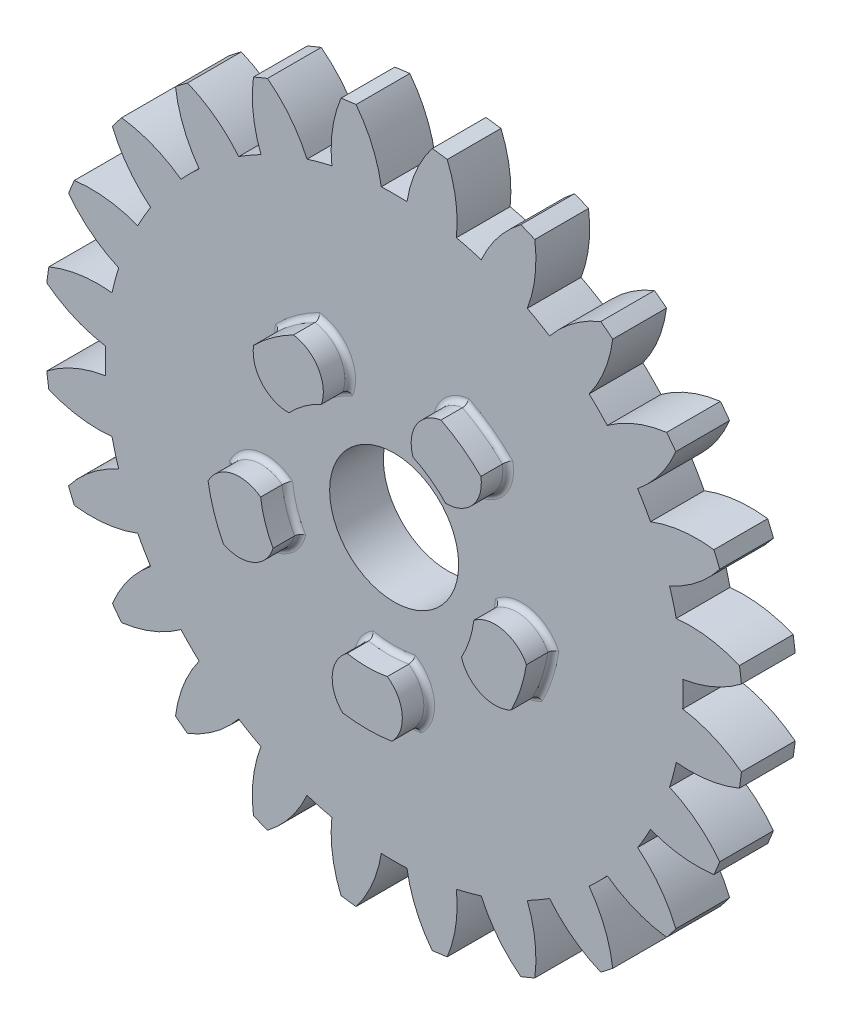
SolidWorks part; units mm, degrees
ref_plane "Front Plane" through (0, 0, 0) normal (0, 0, 1) x (1, 0, 0)
ref_plane "Top Plane" through (0, 0, 0) normal (0, 1, 0) x (1, 0, 0)
ref_plane "Right Plane" through (0, 0, 0) normal (1, 0, 0) x (0, 0, -1)
sketch "Sketch1" plane through (0, 0, 0) normal (0, 0, 1) x (1, 0, 0)
  circle A0 centre (0, 0) radius 3
  arc A96 (-32.3065, 3.5416) -> (-26.8474, 1.1963) centre (-24.9877, 13.0513) ccw
  arc A97 (-26.8474, 1.1963) -> (-26.8474, -1.1963) centre (0, 0) ccw
  arc A98 (-26.8474, -1.1963) -> (-32.3065, -3.5416) centre (-24.9877, -13.0513) ccw
  arc A99 (-32.3065, -3.5416) -> (-32.1223, -4.9406) centre (0, 0) ccw
  arc A100 (-32.1223, -4.9406) -> (-26.2422, -5.7931) centre (-27.5142, 6.1393) ccw
  arc A101 (-26.2422, -5.7931) -> (-25.6229, -8.1041) centre (0, 0) ccw
  arc A102 (-25.6229, -8.1041) -> (-30.289, -11.7824) centre (-20.7583, -19.0739) ccw
  arc A103 (-30.289, -11.7824) -> (-29.749, -13.0861) centre (0, 0) ccw
  arc A104 (-29.749, -13.0861) -> (-23.8486, -12.3877) centre (-28.1656, -1.191) ccw
  arc A105 (-23.8486, -12.3877) -> (-22.6523, -14.4597) centre (0, 0) ccw
  arc A106 (-22.6523, -14.4597) -> (-26.2074, -19.2203) centre (-15.1143, -23.7966) ccw
  arc A107 (-26.2074, -19.2203) -> (-25.3484, -20.3398) centre (0, 0) ccw
  arc A108 (-25.3484, -20.3398) -> (-19.8299, -18.138) centre (-26.8976, -8.4403) ccw
  arc A109 (-19.8299, -18.138) -> (-18.138, -19.8299) centre (0, 0) ccw
  arc A110 (-18.138, -19.8299) -> (-20.3398, -25.3484) centre (-8.4403, -26.8976) ccw
  arc A111 (-20.3398, -25.3484) -> (-19.2203, -26.2074) centre (0, 0) ccw
  arc A112 (-19.2203, -26.2074) -> (-14.4597, -22.6523) centre (-23.7966, -15.1143) ccw
  arc A113 (-14.4597, -22.6523) -> (-12.3877, -23.8486) centre (0, 0) ccw
  arc A114 (-12.3877, -23.8486) -> (-13.0861, -29.749) centre (-1.191, -28.1656) ccw
  arc A115 (-13.0861, -29.749) -> (-11.7824, -30.289) centre (0, 0) ccw
  arc A116 (-11.7824, -30.289) -> (-8.1041, -25.6229) centre (-19.0739, -20.7583) ccw
  arc A117 (-8.1041, -25.6229) -> (-5.7931, -26.2422) centre (0, 0) ccw
  arc A118 (-5.7931, -26.2422) -> (-4.9406, -32.1223) centre (6.1393, -27.5142) ccw
  arc A119 (-4.9406, -32.1223) -> (-3.5416, -32.3065) centre (0, 0) ccw
  arc A120 (-3.5416, -32.3065) -> (-1.1963, -26.8474) centre (-13.0513, -24.9877) ccw
  arc A121 (-1.1963, -26.8474) -> (1.1963, -26.8474) centre (0, 0) ccw
  arc A122 (1.1963, -26.8474) -> (3.5416, -32.3065) centre (13.0513, -24.9877) ccw
  arc A123 (3.5416, -32.3065) -> (4.9406, -32.1223) centre (0, 0) ccw
  arc A124 (4.9406, -32.1223) -> (5.7931, -26.2422) centre (-6.1393, -27.5142) ccw
  arc A125 (5.7931, -26.2422) -> (8.1041, -25.6229) centre (0, 0) ccw
  arc A126 (8.1041, -25.6229) -> (11.7824, -30.289) centre (19.0739, -20.7583) ccw
  arc A127 (11.7824, -30.289) -> (13.0861, -29.749) centre (0, 0) ccw
  arc A128 (13.0861, -29.749) -> (12.3877, -23.8486) centre (1.191, -28.1656) ccw
  arc A129 (12.3877, -23.8486) -> (14.4597, -22.6523) centre (0, 0) ccw
  arc A130 (14.4597, -22.6523) -> (19.2203, -26.2074) centre (23.7966, -15.1143) ccw
  arc A131 (19.2203, -26.2074) -> (20.3398, -25.3484) centre (0, 0) ccw
  arc A132 (20.3398, -25.3484) -> (18.138, -19.8299) centre (8.4403, -26.8976) ccw
  arc A133 (18.138, -19.8299) -> (19.8299, -18.138) centre (0, 0) ccw
  arc A134 (19.8299, -18.138) -> (25.3484, -20.3398) centre (26.8976, -8.4403) ccw
  arc A135 (25.3484, -20.3398) -> (26.2074, -19.2203) centre (0, 0) ccw
  arc A136 (26.2074, -19.2203) -> (22.6523, -14.4597) centre (15.1143, -23.7966) ccw
  arc A137 (22.6523, -14.4597) -> (23.8486, -12.3877) centre (0, 0) ccw
  arc A138 (23.8486, -12.3877) -> (29.749, -13.0861) centre (28.1656, -1.191) ccw
  arc A139 (29.749, -13.0861) -> (30.289, -11.7824) centre (0, 0) ccw
  arc A140 (30.289, -11.7824) -> (25.6229, -8.1041) centre (20.7583, -19.0739) ccw
  arc A141 (25.6229, -8.1041) -> (26.2422, -5.7931) centre (0, 0) ccw
  arc A142 (26.2422, -5.7931) -> (32.1223, -4.9406) centre (27.5142, 6.1393) ccw
  arc A143 (32.1223, -4.9406) -> (32.3065, -3.5416) centre (0, 0) ccw
  arc A144 (32.3065, -3.5416) -> (26.8474, -1.1963) centre (24.9877, -13.0513) ccw
  arc A145 (26.8474, -1.1963) -> (26.8474, 1.1963) centre (0, 0) ccw
  arc A146 (26.8474, 1.1963) -> (32.3065, 3.5416) centre (24.9877, 13.0513) ccw
  arc A147 (32.3065, 3.5416) -> (32.1223, 4.9406) centre (0, 0) ccw
  arc A148 (32.1223, 4.9406) -> (26.2422, 5.7931) centre (27.5142, -6.1393) ccw
  arc A149 (26.2422, 5.7931) -> (25.6229, 8.1041) centre (0, 0) ccw
  arc A150 (25.6229, 8.1041) -> (30.289, 11.7824) centre (20.7583, 19.0739) ccw
  arc A151 (30.289, 11.7824) -> (29.749, 13.0861) centre (0, 0) ccw
  arc A152 (29.749, 13.0861) -> (23.8486, 12.3877) centre (28.1656, 1.191) ccw
  arc A153 (23.8486, 12.3877) -> (22.6523, 14.4597) centre (0, 0) ccw
  arc A154 (22.6523, 14.4597) -> (26.2074, 19.2203) centre (15.1143, 23.7966) ccw
  arc A155 (26.2074, 19.2203) -> (25.3484, 20.3398) centre (0, 0) ccw
  arc A156 (25.3484, 20.3398) -> (19.8299, 18.138) centre (26.8976, 8.4403) ccw
  arc A157 (19.8299, 18.138) -> (18.138, 19.8299) centre (0, 0) ccw
  arc A158 (18.138, 19.8299) -> (20.3398, 25.3484) centre (8.4403, 26.8976) ccw
  arc A159 (20.3398, 25.3484) -> (19.2203, 26.2074) centre (0, 0) ccw
  arc A160 (19.2203, 26.2074) -> (14.4597, 22.6523) centre (23.7966, 15.1143) ccw
  arc A161 (14.4597, 22.6523) -> (12.3877, 23.8486) centre (0, 0) ccw
  arc A162 (12.3877, 23.8486) -> (13.0861, 29.749) centre (1.191, 28.1656) ccw
  arc A163 (13.0861, 29.749) -> (11.7824, 30.289) centre (0, 0) ccw
  arc A164 (11.7824, 30.289) -> (8.1041, 25.6229) centre (19.0739, 20.7583) ccw
  arc A165 (8.1041, 25.6229) -> (5.7931, 26.2422) centre (0, 0) ccw
  arc A166 (5.7931, 26.2422) -> (4.9406, 32.1223) centre (-6.1393, 27.5142) ccw
  arc A167 (4.9406, 32.1223) -> (3.5416, 32.3065) centre (0, 0) ccw
  arc A168 (3.5416, 32.3065) -> (1.1963, 26.8474) centre (13.0513, 24.9877) ccw
  arc A169 (1.1963, 26.8474) -> (-1.1963, 26.8474) centre (0, 0) ccw
  arc A170 (-1.1963, 26.8474) -> (-3.5416, 32.3065) centre (-13.0513, 24.9877) ccw
  arc A171 (-3.5416, 32.3065) -> (-4.9406, 32.1223) centre (0, 0) ccw
  arc A172 (-4.9406, 32.1223) -> (-5.7931, 26.2422) centre (6.1393, 27.5142) ccw
  arc A173 (-5.7931, 26.2422) -> (-8.1041, 25.6229) centre (0, 0) ccw
  arc A174 (-8.1041, 25.6229) -> (-11.7824, 30.289) centre (-19.0739, 20.7583) ccw
  arc A175 (-11.7824, 30.289) -> (-13.0861, 29.749) centre (0, 0) ccw
  arc A176 (-13.0861, 29.749) -> (-12.3877, 23.8486) centre (-1.191, 28.1656) ccw
  arc A177 (-12.3877, 23.8486) -> (-14.4597, 22.6523) centre (0, 0) ccw
  arc A178 (-14.4597, 22.6523) -> (-19.2203, 26.2074) centre (-23.7966, 15.1143) ccw
  arc A179 (-19.2203, 26.2074) -> (-20.3398, 25.3484) centre (0, 0) ccw
  arc A180 (-20.3398, 25.3484) -> (-18.138, 19.8299) centre (-8.4403, 26.8976) ccw
  arc A181 (-18.138, 19.8299) -> (-19.8299, 18.138) centre (0, 0) ccw
  arc A182 (-19.8299, 18.138) -> (-25.3484, 20.3398) centre (-26.8976, 8.4403) ccw
  arc A183 (-25.3484, 20.3398) -> (-26.2074, 19.2203) centre (0, 0) ccw
  arc A184 (-26.2074, 19.2203) -> (-22.6523, 14.4597) centre (-15.1143, 23.7966) ccw
  arc A185 (-22.6523, 14.4597) -> (-23.8486, 12.3877) centre (0, 0) ccw
  arc A186 (-23.8486, 12.3877) -> (-29.749, 13.0861) centre (-28.1656, 1.191) ccw
  arc A187 (-29.749, 13.0861) -> (-30.289, 11.7824) centre (0, 0) ccw
  arc A188 (-30.289, 11.7824) -> (-25.6229, 8.1041) centre (-20.7583, 19.0739) ccw
  arc A189 (-25.6229, 8.1041) -> (-26.2422, 5.7931) centre (0, 0) ccw
  arc A190 (-26.2422, 5.7931) -> (-32.1223, 4.9406) centre (-27.5142, -6.1393) ccw
  arc A191 (-32.1223, 4.9406) -> (-32.3065, 3.5416) centre (0, 0) ccw
  arc A192 (-32.3065, 3.5416) -> (-26.8474, 1.1963) centre (-24.9877, 13.0513) ccw
  arc A193 (-26.8474, 1.1963) -> (-26.8474, -1.1963) centre (0, 0) ccw
  arc A194 (-26.8474, -1.1963) -> (-32.3065, -3.5416) centre (-24.9877, -13.0513) ccw
  arc A195 (-32.3065, -3.5416) -> (-32.1223, -4.9406) centre (0, 0) ccw
  arc A196 (-32.1223, -4.9406) -> (-26.2422, -5.7931) centre (-27.5142, 6.1393) ccw
  arc A197 (-26.2422, -5.7931) -> (-25.6229, -8.1041) centre (0, 0) ccw
  arc A198 (-25.6229, -8.1041) -> (-30.289, -11.7824) centre (-20.7583, -19.0739) ccw
  arc A199 (-30.289, -11.7824) -> (-29.749, -13.0861) centre (0, 0) ccw
  arc A200 (-29.749, -13.0861) -> (-23.8486, -12.3877) centre (-28.1656, -1.191) ccw
  arc A201 (-23.8486, -12.3877) -> (-22.6523, -14.4597) centre (0, 0) ccw
  arc A202 (-22.6523, -14.4597) -> (-26.2074, -19.2203) centre (-15.1143, -23.7966) ccw
  arc A203 (-26.2074, -19.2203) -> (-25.3484, -20.3398) centre (0, 0) ccw
  arc A204 (-25.3484, -20.3398) -> (-19.8299, -18.138) centre (-26.8976, -8.4403) ccw
  arc A205 (-19.8299, -18.138) -> (-18.138, -19.8299) centre (0, 0) ccw
  arc A206 (-18.138, -19.8299) -> (-20.3398, -25.3484) centre (-8.4403, -26.8976) ccw
  arc A207 (-20.3398, -25.3484) -> (-19.2203, -26.2074) centre (0, 0) ccw
  arc A208 (-19.2203, -26.2074) -> (-14.4597, -22.6523) centre (-23.7966, -15.1143) ccw
  arc A209 (-14.4597, -22.6523) -> (-12.3877, -23.8486) centre (0, 0) ccw
  arc A210 (-12.3877, -23.8486) -> (-13.0861, -29.749) centre (-1.191, -28.1656) ccw
  arc A211 (-13.0861, -29.749) -> (-11.7824, -30.289) centre (0, 0) ccw
  arc A212 (-11.7824, -30.289) -> (-8.1041, -25.6229) centre (-19.0739, -20.7583) ccw
  arc A213 (-8.1041, -25.6229) -> (-5.7931, -26.2422) centre (0, 0) ccw
  arc A214 (-5.7931, -26.2422) -> (-4.9406, -32.1223) centre (6.1393, -27.5142) ccw
  arc A215 (-4.9406, -32.1223) -> (-3.5416, -32.3065) centre (0, 0) ccw
  arc A216 (-3.5416, -32.3065) -> (-1.1963, -26.8474) centre (-13.0513, -24.9877) ccw
  arc A217 (-1.1963, -26.8474) -> (1.1963, -26.8474) centre (0, 0) ccw
  arc A218 (1.1963, -26.8474) -> (3.5416, -32.3065) centre (13.0513, -24.9877) ccw
  arc A219 (3.5416, -32.3065) -> (4.9406, -32.1223) centre (0, 0) ccw
  arc A220 (4.9406, -32.1223) -> (5.7931, -26.2422) centre (-6.1393, -27.5142) ccw
  arc A221 (5.7931, -26.2422) -> (8.1041, -25.6229) centre (0, 0) ccw
  arc A222 (8.1041, -25.6229) -> (11.7824, -30.289) centre (19.0739, -20.7583) ccw
  arc A223 (11.7824, -30.289) -> (13.0861, -29.749) centre (0, 0) ccw
  arc A224 (13.0861, -29.749) -> (12.3877, -23.8486) centre (1.191, -28.1656) ccw
  arc A225 (12.3877, -23.8486) -> (14.4597, -22.6523) centre (0, 0) ccw
  arc A226 (14.4597, -22.6523) -> (19.2203, -26.2074) centre (23.7966, -15.1143) ccw
  arc A227 (19.2203, -26.2074) -> (20.3398, -25.3484) centre (0, 0) ccw
  arc A228 (20.3398, -25.3484) -> (18.138, -19.8299) centre (8.4403, -26.8976) ccw
  arc A229 (18.138, -19.8299) -> (19.8299, -18.138) centre (0, 0) ccw
  arc A230 (19.8299, -18.138) -> (25.3484, -20.3398) centre (26.8976, -8.4403) ccw
  arc A231 (25.3484, -20.3398) -> (26.2074, -19.2203) centre (0, 0) ccw
  arc A232 (26.2074, -19.2203) -> (22.6523, -14.4597) centre (15.1143, -23.7966) ccw
  arc A233 (22.6523, -14.4597) -> (23.8486, -12.3877) centre (0, 0) ccw
  arc A234 (23.8486, -12.3877) -> (29.749, -13.0861) centre (28.1656, -1.191) ccw
  arc A235 (29.749, -13.0861) -> (30.289, -11.7824) centre (0, 0) ccw
  arc A236 (30.289, -11.7824) -> (25.6229, -8.1041) centre (20.7583, -19.0739) ccw
  arc A237 (25.6229, -8.1041) -> (26.2422, -5.7931) centre (0, 0) ccw
  arc A238 (26.2422, -5.7931) -> (32.1223, -4.9406) centre (27.5142, 6.1393) ccw
  arc A239 (32.1223, -4.9406) -> (32.3065, -3.5416) centre (0, 0) ccw
  arc A240 (32.3065, -3.5416) -> (26.8474, -1.1963) centre (24.9877, -13.0513) ccw
  arc A241 (26.8474, -1.1963) -> (26.8474, 1.1963) centre (0, 0) ccw
  arc A242 (26.8474, 1.1963) -> (32.3065, 3.5416) centre (24.9877, 13.0513) ccw
  arc A243 (32.3065, 3.5416) -> (32.1223, 4.9406) centre (0, 0) ccw
  arc A244 (32.1223, 4.9406) -> (26.2422, 5.7931) centre (27.5142, -6.1393) ccw
  arc A245 (26.2422, 5.7931) -> (25.6229, 8.1041) centre (0, 0) ccw
  arc A246 (25.6229, 8.1041) -> (30.289, 11.7824) centre (20.7583, 19.0739) ccw
  arc A247 (30.289, 11.7824) -> (29.749, 13.0861) centre (0, 0) ccw
  arc A248 (29.749, 13.0861) -> (23.8486, 12.3877) centre (28.1656, 1.191) ccw
  arc A249 (23.8486, 12.3877) -> (22.6523, 14.4597) centre (0, 0) ccw
  arc A250 (22.6523, 14.4597) -> (26.2074, 19.2203) centre (15.1143, 23.7966) ccw
  arc A251 (26.2074, 19.2203) -> (25.3484, 20.3398) centre (0, 0) ccw
  arc A252 (25.3484, 20.3398) -> (19.8299, 18.138) centre (26.8976, 8.4403) ccw
  arc A253 (19.8299, 18.138) -> (18.138, 19.8299) centre (0, 0) ccw
  arc A254 (18.138, 19.8299) -> (20.3398, 25.3484) centre (8.4403, 26.8976) ccw
  arc A255 (20.3398, 25.3484) -> (19.2203, 26.2074) centre (0, 0) ccw
  arc A256 (19.2203, 26.2074) -> (14.4597, 22.6523) centre (23.7966, 15.1143) ccw
  arc A257 (14.4597, 22.6523) -> (12.3877, 23.8486) centre (0, 0) ccw
  arc A258 (12.3877, 23.8486) -> (13.0861, 29.749) centre (1.191, 28.1656) ccw
  arc A259 (13.0861, 29.749) -> (11.7824, 30.289) centre (0, 0) ccw
  arc A260 (11.7824, 30.289) -> (8.1041, 25.6229) centre (19.0739, 20.7583) ccw
  arc A261 (8.1041, 25.6229) -> (5.7931, 26.2422) centre (0, 0) ccw
  arc A262 (5.7931, 26.2422) -> (4.9406, 32.1223) centre (-6.1393, 27.5142) ccw
  arc A263 (4.9406, 32.1223) -> (3.5416, 32.3065) centre (0, 0) ccw
  arc A264 (3.5416, 32.3065) -> (1.1963, 26.8474) centre (13.0513, 24.9877) ccw
  arc A265 (1.1963, 26.8474) -> (-1.1963, 26.8474) centre (0, 0) ccw
  arc A266 (-1.1963, 26.8474) -> (-3.5416, 32.3065) centre (-13.0513, 24.9877) ccw
  arc A267 (-3.5416, 32.3065) -> (-4.9406, 32.1223) centre (0, 0) ccw
  arc A268 (-4.9406, 32.1223) -> (-5.7931, 26.2422) centre (6.1393, 27.5142) ccw
  arc A269 (-5.7931, 26.2422) -> (-8.1041, 25.6229) centre (0, 0) ccw
  arc A270 (-8.1041, 25.6229) -> (-11.7824, 30.289) centre (-19.0739, 20.7583) ccw
  arc A271 (-11.7824, 30.289) -> (-13.0861, 29.749) centre (0, 0) ccw
  arc A272 (-13.0861, 29.749) -> (-12.3877, 23.8486) centre (-1.191, 28.1656) ccw
  arc A273 (-12.3877, 23.8486) -> (-14.4597, 22.6523) centre (0, 0) ccw
  arc A274 (-14.4597, 22.6523) -> (-19.2203, 26.2074) centre (-23.7966, 15.1143) ccw
  arc A275 (-19.2203, 26.2074) -> (-20.3398, 25.3484) centre (0, 0) ccw
  arc A276 (-20.3398, 25.3484) -> (-18.138, 19.8299) centre (-8.4403, 26.8976) ccw
  arc A277 (-18.138, 19.8299) -> (-19.8299, 18.138) centre (0, 0) ccw
  arc A278 (-19.8299, 18.138) -> (-25.3484, 20.3398) centre (-26.8976, 8.4403) ccw
  arc A279 (-25.3484, 20.3398) -> (-26.2074, 19.2203) centre (0, 0) ccw
  arc A280 (-26.2074, 19.2203) -> (-22.6523, 14.4597) centre (-15.1143, 23.7966) ccw
  arc A281 (-22.6523, 14.4597) -> (-23.8486, 12.3877) centre (0, 0) ccw
  arc A282 (-23.8486, 12.3877) -> (-29.749, 13.0861) centre (-28.1656, 1.191) ccw
  arc A283 (-29.749, 13.0861) -> (-30.289, 11.7824) centre (0, 0) ccw
  arc A284 (-30.289, 11.7824) -> (-25.6229, 8.1041) centre (-20.7583, 19.0739) ccw
  arc A285 (-25.6229, 8.1041) -> (-26.2422, 5.7931) centre (0, 0) ccw
  arc A286 (-26.2422, 5.7931) -> (-32.1223, 4.9406) centre (-27.5142, -6.1393) ccw
  arc A287 (-32.1223, 4.9406) -> (-32.3065, 3.5416) centre (0, 0) ccw
  dimension "D1" = 0
extrude "Boss-Extrude1" add sketch "Sketch1" along normal blind 5 contours A0 | A192 A193 A194 A195 A196 A197 A198 A199 A200 A201 A202 A203 A204 A205 A206 A207 A208 A209 A210 A211 A212 A213 A214 A215 A216 A217 A218 A219 A220 A221 A222 A223 A224 A225 A226 A227 A228 A229 A230 A231 A232 A233 A234 A235 A236 A237 A238 A239 A240 A241 A242 A243 A244 A245 A246 A247 A248 A249 A250 A251 A252 A253 A254 A255 A256 A257 A258 A259 A260 A261 A262 A263 A264 A265 A266 A267 A268 A269 A270 A271 A272 A273 A274 A275 A276 A277 A278 A279 A280 A281 A282 A283 A284 A285 A286 A287 region at (0, 0, 0)
sketch "Sketch2" plane through (0, 0, 0) normal (0, 0, -1) x (-1, 0, 0)
  circle A0 centre (0, 0) radius 6
extrude "Cut-Extrude1" cut sketch "Sketch2" against normal up to next
sketch "Sketch3" plane through (0, 0, 5) normal (0, 0, 1) x (1, 0, 0)
  arc A0 (2.2906, -14.8241) -> (13.3907, -6.7594) centre (0, 0) ccw
  arc A1 (8.7662, -4.8119) -> (13.3907, -6.7594) centre (11.8882, -3.8627) ccw
  arc A2 (1.8675, -9.8241) -> (8.7662, -4.8119) centre (0, 0) ccw
  arc A3 (2.2906, -14.8241) -> (1.8675, -9.8241) centre (0, -12.5) ccw
  arc A4 (-8.7662, -4.8119) -> (-1.8675, -9.8241) centre (0, 0) ccw
  arc A5 (-13.3907, -6.7594) -> (-8.7662, -4.8119) centre (-11.8882, -3.8627) ccw
  arc A6 (-13.3907, -6.7594) -> (-2.2906, -14.8241) centre (0, 0) ccw
  arc A7 (-1.8675, -9.8241) -> (-2.2906, -14.8241) centre (0, -12.5) ccw
  arc A8 (-7.2853, 6.8501) -> (-9.9203, -1.2597) centre (0, 0) ccw
  arc A9 (-10.5665, 10.6465) -> (-7.2853, 6.8501) centre (-7.3473, 10.1127) ccw
  arc A10 (-10.5665, 10.6465) -> (-14.8064, -2.4024) centre (0, 0) ccw
  arc A11 (-9.9203, -1.2597) -> (-14.8064, -2.4024) centre (-11.8882, -3.8627) ccw
  arc A12 (4.2636, 9.0455) -> (-4.2636, 9.0455) centre (0, 0) ccw
  arc A13 (6.8602, 13.3393) -> (4.2636, 9.0455) centre (7.3473, 10.1127) ccw
  arc A14 (6.8602, 13.3393) -> (-6.8602, 13.3393) centre (0, 0) ccw
  arc A15 (-4.2636, 9.0455) -> (-6.8602, 13.3393) centre (-7.3473, 10.1127) ccw
  arc A16 (9.9203, -1.2597) -> (7.2853, 6.8501) centre (0, 0) ccw
  arc A17 (14.8064, -2.4024) -> (9.9203, -1.2597) centre (11.8882, -3.8627) ccw
  arc A18 (14.8064, -2.4024) -> (10.5665, 10.6465) centre (0, 0) ccw
  arc A19 (7.2853, 6.8501) -> (10.5665, 10.6465) centre (7.3473, 10.1127) ccw
  arc A20 (-13.3907, -6.7594) -> (-14.8064, -2.4024) centre (0, 0) cw
  arc A21 (-9.9203, -1.2597) -> (-8.7662, -4.8119) centre (0, 0) ccw
  arc A22 (-4.2636, 9.0455) -> (-7.2853, 6.8501) centre (0, 0) ccw
  arc A23 (-10.5665, 10.6465) -> (-6.8602, 13.3393) centre (0, 0) cw
  arc A24 (7.2853, 6.8501) -> (4.2636, 9.0455) centre (0, 0) ccw
  arc A25 (6.8602, 13.3393) -> (10.5665, 10.6465) centre (0, 0) cw
  arc A26 (8.7662, -4.8119) -> (9.9203, -1.2597) centre (0, 0) ccw
  arc A27 (14.8064, -2.4024) -> (13.3907, -6.7594) centre (0, 0) cw
  arc A28 (-1.8675, -9.8241) -> (1.8675, -9.8241) centre (0, 0) ccw
  arc A29 (2.2906, -14.8241) -> (-2.2906, -14.8241) centre (0, 0) cw
  dimension "D1" = 5
extrude "Boss-Extrude2" add sketch "Sketch3" along normal blind 2.5 contours A23 A9 A22 A15 | A25 A13 A24 A19 | A21 A11 A20 A5 | A29 A3 A28 A7 | A27 A17 A26 A1 region at (0, -12.4574, 5) region at (11.8477, -3.8496, 5) region at (-11.8477, -3.8496, 5) region at (7.3223, 10.0783, 5) region at (-7.3223, 10.0783, 5)
fillet "Fillet1" radius 0.5 20 edges at (-14.2658, -4.6353, 5) (-12.6313, -0.6853, 5) (-3.2515, -12.2249, 5) (0, -10, 5) (-9.5106, -3.0902, 5) (-10.6218, -6.8701, 5) (0, -15, 5) (3.2515, -12.2249, 5) (9.5106, -3.0902, 5) (10.6218, -6.8701, 5) (14.2658, -4.6353, 5) (12.6313, -0.6853, 5) (4.555, 11.8013, 5) (8.8168, 12.1353, 5) (9.8161, 7.9789, 5) (5.8779, 8.0902, 5) (-9.8161, 7.9789, 5) (-8.8168, 12.1353, 5) (-4.555, 11.8013, 5) (-5.8779, 8.0902, 5)
